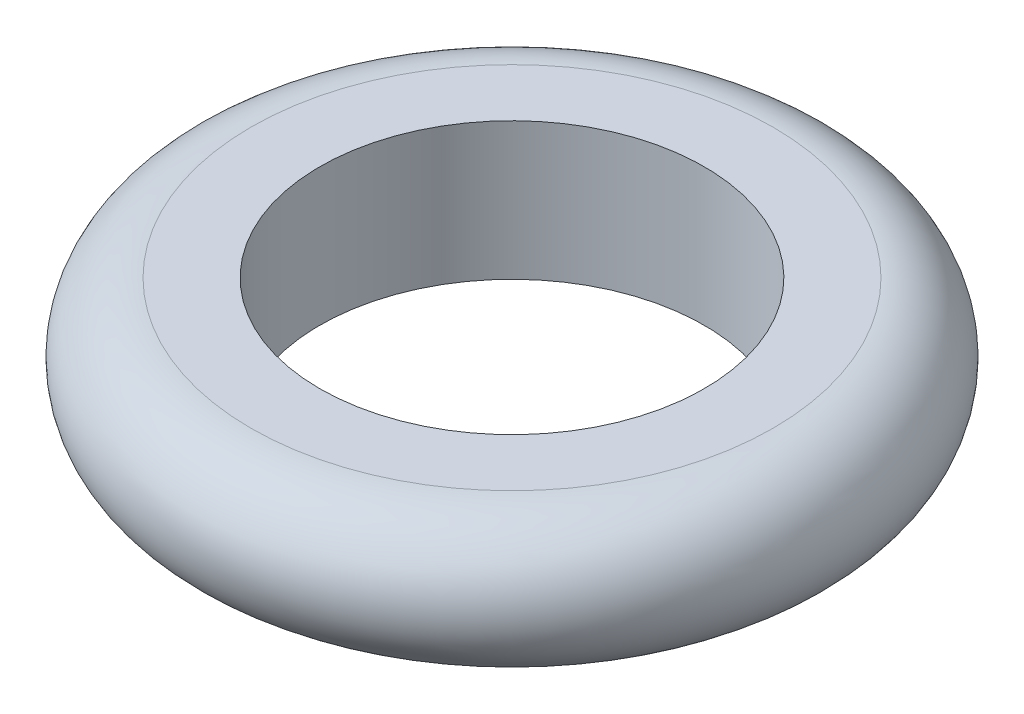
SolidWorks part; units mm, degrees
material "Rubber"
ref_plane "Front" through (0, 0, 0) normal (0, 0, 1) x (1, 0, 0)
ref_plane "Top" through (0, 0, 0) normal (0, 1, 0) x (1, 0, 0)
ref_plane "Right" through (0, 0, 0) normal (1, 0, 0) x (0, 0, -1)
sketch "Sketch1" plane through (0, 0, 0) normal (0, 1, 0) x (1, 0, 0)
  circle A0 centre (0, 0) radius 70
  circle A1 centre (0, 0) radius 120
  dimension "D1" = 240
  dimension "D2" = 50
extrude "Boss-Extrude1" add sketch "Sketch1" along normal blind 50
fillet "Fillet2" 2 edges at (0, 0, 120) (0, 50, 120) type full round first side face at (0, 0, 120) second side face at (0, 50, 120) middle face at (0, 50, 120)
